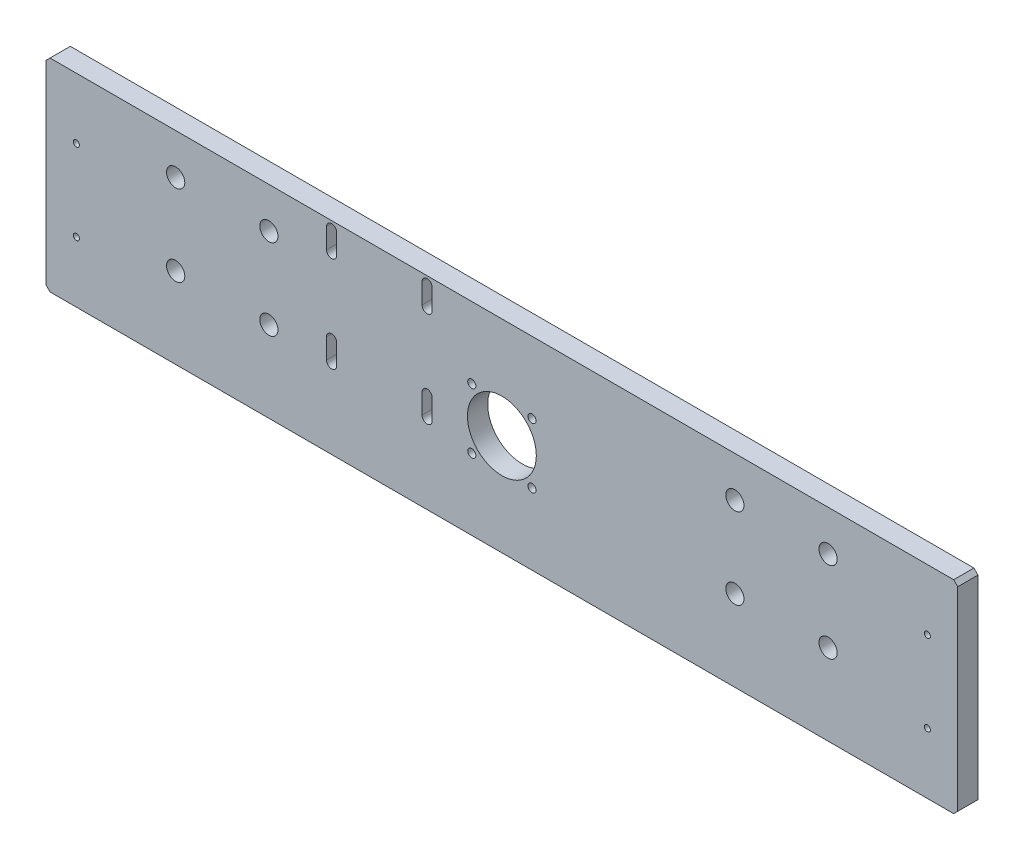
SolidWorks part; units mm, degrees
ref_plane "Piano frontale" through (0, 0, 0) normal (0, 0, 1) x (1, 0, 0)
ref_plane "Piano superiore" through (0, 0, 0) normal (0, 1, 0) x (1, 0, 0)
ref_plane "Piano destro" through (0, 0, 0) normal (1, 0, 0) x (0, 0, -1)
sketch "Schizzo1" plane through (0, 0, 0) normal (0, 0, 1) x (1, 0, 0)
  line L0 (225, 100) -> (225, 0) construction
  line L1 (2, 0) -> (448, 0)
  line L2 (0, 2) -> (0, 98)
  line L3 (2, 100) -> (448, 100)
  line L4 (450, 2) -> (450, 98)
  line L5 (87, 100) -> (87, 0) construction
  line L7 (225, 50) -> (243.5099, 50) construction
  line L9 (225, 50) -> (205.51, 69.49) construction
  line L21 (0, 98) -> (2, 100)
  line L22 (2, 0) -> (0, 2)
  line L23 (448, 0) -> (450, 2)
  line L24 (448, 100) -> (450, 98)
  circle A0 centre (225, 50) radius 17
  circle A1 centre (225, 50) radius 21 construction
  circle A2 centre (239.8492, 64.8492) radius 2
  circle A3 centre (239.8492, 35.1508) radius 2
  circle A4 centre (210.1508, 35.1508) radius 2
  circle A5 centre (386, 40) radius 4.5
  circle A6 centre (386, 80) radius 4.5
  circle A7 centre (340, 40) radius 4.5
  circle A8 centre (340, 80) radius 4.5
  circle A9 centre (435, 70) radius 1.5
  circle A10 centre (435, 30) radius 1.5
  circle A11 centre (15, 30) radius 1.5
  circle A13 centre (210.1508, 64.8492) radius 2
  circle A18 centre (15, 70) radius 1.5
  circle A29 centre (110, 80) radius 4.5
  circle A30 centre (110, 40) radius 4.5
  circle A32 centre (64, 80) radius 4.5
  circle A33 centre (64, 40) radius 4.5
  point P0 (0, 0)
  point P1 (450, 100)
  point P2 (0, 100)
  point P3 (450, 0)
  point P9 (210.1508, 64.8492)
  point P13 (210.1508, 64.8492)
  dimension "D4" = 34
  dimension "D10" = 23
  dimension "D15" = 3
  dimension "D17" = 4
  dimension "D8" = 45
  dimension "D5" = 42
  dimension "D9" = 64
  dimension "D11" = 9
  dimension "D1" = 100
  dimension "D2" = 450
  dimension "D6" = 20
  dimension "D7" = 40
  dimension "D14" = 30
  dimension "D16" = 15
extrude "Boss-Extrude1" add sketch "Schizzo1" against normal blind 10
sketch "Sketch1" plane through (0, 0, -10) normal (0, 0, -1) x (-1, 0, 0)
  line L0 (-188.1012, 91.2484) -> (-188.1012, 44.1084) construction
  line L1 (-140.9612, 91.2484) -> (-140.9612, 44.1084) construction
  line L2 (-188.1012, 86.2484) -> (-188.1012, 96.2484) construction
  line L3 (-190.6012, 86.2484) -> (-190.6012, 96.2484)
  line L4 (-185.6012, 86.2484) -> (-185.6012, 96.2484)
  line L5 (-188.1012, 67.6784) -> (-140.9612, 67.6784) construction
  line L6 (-164.5312, 67.6784) -> (-164.5312, 85.2274) construction
  line L7 (-140.9612, 86.2484) -> (-140.9612, 96.2484) construction
  line L8 (-143.4612, 86.2484) -> (-143.4612, 96.2484)
  line L9 (-138.4612, 86.2484) -> (-138.4612, 96.2484)
  line L10 (-188.1012, 39.1084) -> (-188.1012, 49.1084) construction
  line L11 (-190.6012, 39.1084) -> (-190.6012, 49.1084)
  line L12 (-185.6012, 39.1084) -> (-185.6012, 49.1084)
  line L13 (-140.9612, 39.1084) -> (-140.9612, 49.1084) construction
  line L14 (-143.4612, 39.1084) -> (-143.4612, 49.1084)
  line L15 (-138.4612, 39.1084) -> (-138.4612, 49.1084)
  arc A0 (-190.6012, 86.2484) -> (-185.6012, 86.2484) centre (-188.1012, 86.2484) ccw
  arc A1 (-185.6012, 96.2484) -> (-190.6012, 96.2484) centre (-188.1012, 96.2484) ccw
  arc A2 (-143.4612, 86.2484) -> (-138.4612, 86.2484) centre (-140.9612, 86.2484) ccw
  arc A3 (-138.4612, 96.2484) -> (-143.4612, 96.2484) centre (-140.9612, 96.2484) ccw
  arc A4 (-190.6012, 39.1084) -> (-185.6012, 39.1084) centre (-188.1012, 39.1084) ccw
  arc A5 (-185.6012, 49.1084) -> (-190.6012, 49.1084) centre (-188.1012, 49.1084) ccw
  arc A6 (-143.4612, 39.1084) -> (-138.4612, 39.1084) centre (-140.9612, 39.1084) ccw
  arc A7 (-138.4612, 49.1084) -> (-143.4612, 49.1084) centre (-140.9612, 49.1084) ccw
  point P10 (-188.1012, 91.2484)
  point P22 (-140.9612, 91.2484)
  point P28 (-188.1012, 44.1084)
  point P35 (-140.9612, 44.1084)
  dimension "D1" = 10
  dimension "D2" = 5
  dimension "D3" = 5
  dimension "D4" = 5
  dimension "D5" = 5
extrude "Cut-Extrude1" cut sketch "Sketch1" against normal through all
